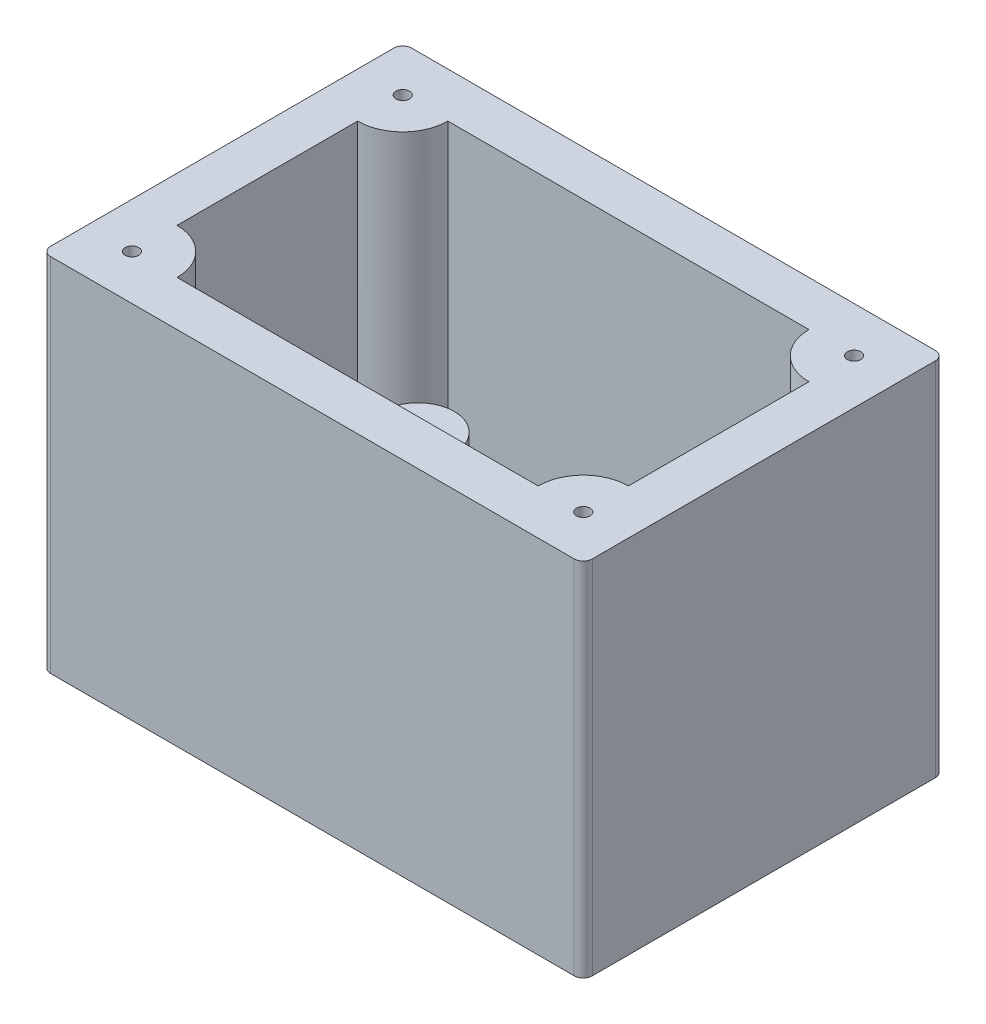
SolidWorks part; units mm, degrees
ref_plane "Front Plane" through (0, 0, 0) normal (0, 0, 1) x (1, 0, 0)
ref_plane "Top Plane" through (0, 0, 0) normal (0, 1, 0) x (1, 0, 0)
ref_plane "Right Plane" through (0, 0, 0) normal (1, 0, 0) x (0, 0, -1)
sketch "Sketch1" plane through (0, 0, 0) normal (0, 1, 0) x (1, 0, 0)
  line L1 (0, 0) -> (50, 0)
  line L2 (0, 0) -> (0, -30)
  line L3 (0, -30) -> (50, -30)
  line L4 (50, 0) -> (50, -30)
  line L5 (-5, 5) -> (55, 5)
  line L6 (-5, 5) -> (-5, -35)
  line L7 (-5, -35) -> (55, -35)
  line L8 (55, 5) -> (55, -35)
  dimension "D1" = 50
  dimension "D2" = 30
  dimension "D3" = 5
  dimension "D4" = 5
  dimension "D5" = 5
  dimension "D6" = 5
extrude "Boss-Extrude1" add sketch "Sketch1" along normal blind 5 contours L2 L1 L4 L3
extrude "Boss-Extrude2" add sketch "Sketch1<3>" along normal blind 40
sketch "Sketch1<3>" plane through (0, 0, 0) normal (0, 1, 0) x (1, 0, 0) same geometry as "Sketch1"
sketch "Sketch2" plane through (0, 5, 0) normal (0, 1, 0) x (1, 0, 0)
  line L0 (0, 0) -> (50, 0) construction
  line L1 (0, -30) -> (50, -30) construction
  line L2 (0, 0) -> (0, -30) construction
  line L3 (50, -30) -> (50, 0) construction
  circle A0 centre (8.2, -6.5) radius 4
  circle A1 centre (41.8, -23.5) radius 4
  dimension "D1" = 6.5
  dimension "D2" = 6.5
  dimension "D3" = 8.2
  dimension "D4" = 8.2
extrude "Boss-Extrude3" add sketch "Sketch2" along normal blind 10
sketch "Sketch6" plane through (0, 15, 0) normal (0, 1, 0) x (1, 0, 0)
  circle A0 centre (41.8, -23.4) radius 0.75
  circle A1 centre (8.1, -6.6) radius 0.75
  dimension "D1" = 1.5
extrude "Cut-Extrude1" cut sketch "Sketch6" against normal blind 5
fillet "Fillet1" radius 1.5 2 edges at (8.2, 5, 2.5) (41.8, 5, 19.5)
sketch "Sketch7" plane through (0, 40, 0) normal (0, 1, 0) x (1, 0, 0)
  line L4 (0, -30) -> (50, -30)
  line L5 (50, -30) -> (50, 0)
  line L6 (50, 0) -> (0, 0)
  line L7 (0, 0) -> (0, -30)
  line L8 (0, -30) -> (50, -30)
  line L9 (50, -30) -> (50, 0)
  line L10 (50, 0) -> (0, 0)
  line L11 (0, 0) -> (0, -30)
  dimension "D1" = 0
sketch "Sketch9" plane through (0, 5, 0) normal (0, 1, 0) x (1, 0, 0)
  line L0 (5, 0) -> (0, 0)
  line L1 (50, -5) -> (50, 0)
  line L2 (45, -30) -> (50, -30)
  line L3 (0, -25) -> (0, -30)
  line L4 (0, -30) -> (50, -30)
  line L5 (50, -30) -> (50, 0)
  line L6 (50, 0) -> (0, 0)
  line L7 (0, 0) -> (0, -30)
  line L8 (0, -30) -> (5, -30)
  line L9 (50, -30) -> (50, -25)
  line L10 (50, 0) -> (45, 0)
  line L11 (0, 0) -> (0, -5)
  arc A0 (50, -25) -> (45, -30) centre (50, -30) ccw
  arc A1 (5, -30) -> (0, -25) centre (0, -30) ccw
  arc A2 (0, -5) -> (5, 0) centre (0, 0) ccw
  arc A3 (45, 0) -> (50, -5) centre (50, 0) ccw
  dimension "D2" = 10
  dimension "D3" = 10
  dimension "D4" = 10
  dimension "D5" = 10
  dimension "D1" = 0
extrude "Boss-Extrude4" add sketch "Sketch9" against normal up to surface (5 mm away) and the other way up to surface (35 mm away) up to face at (25, 0, 15) other way up to face at (25, 40, 15)
sketch "Sketch10" plane through (0, 40, 0) normal (0, 1, 0) x (1, 0, 0)
  line L0 (55, -35) -> (55, 5) construction
  line L2 (-5, -35) -> (55, -35) construction
  line L3 (55, -15) -> (-5, -15) construction
  line L4 (-5, 5) -> (-5, -35) construction
  line L5 (25, -35) -> (25, 5) construction
  line L6 (55, 5) -> (-5, 5) construction
  circle A0 centre (50, -30) radius 0.75
  circle A2 centre (0, -30) radius 0.75
  circle A3 centre (50, 0) radius 0.75
  circle A4 centre (0, 0) radius 0.75
  dimension "D1" = 5
  dimension "D3" = 1.5
  dimension "D2" = 5
extrude "Cut-Extrude2" cut sketch "Sketch10" against normal blind 10
fillet "Fillet2" radius 1 4 edges at (-5, 20, 35) (-5, 20, -5) (55, 20, -5) (55, 20, 35)
